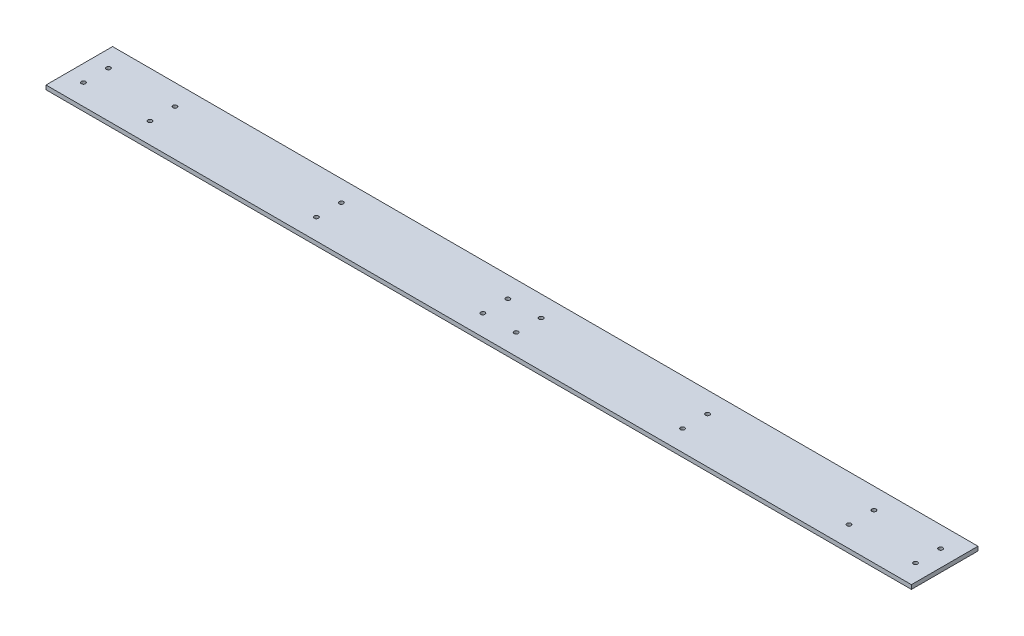
SolidWorks part; units mm, degrees
ref_plane "Front Plane" through (0, 0, 0) normal (0, 0, 1) x (1, 0, 0)
ref_plane "Top Plane" through (0, 0, 0) normal (0, 1, 0) x (1, 0, 0)
ref_plane "Right Plane" through (0, 0, 0) normal (1, 0, 0) x (0, 0, -1)
sketch "Sketch1" plane through (0, 0, 0) normal (0, 1, 0) x (1, 0, 0)
  line L0 (-200, 15) -> (-200, -15) construction
  line L1 (-500, 40) -> (540, 40)
  line L2 (-500, 40) -> (-500, -40)
  line L3 (-500, -40) -> (540, -40)
  line L4 (540, 40) -> (540, -40)
  line L5 (-200, 0) -> (0, 0) construction
  line L6 (0, 15) -> (0, -15) construction
  line L7 (240, 15) -> (240, -15) construction
  line L8 (0, 15) -> (40, 15) construction
  line L9 (40, 15) -> (40, -15) construction
  line L10 (40, -15) -> (0, -15) construction
  line L11 (0, 15) -> (-200, 15) construction
  line L12 (40, -15) -> (240, -15) construction
  line L13 (0, 0) -> (40, 0) construction
  line L14 (40, 0) -> (240, 0) construction
  line L15 (240, 0) -> (540, 0) construction
  line L16 (-200, 0) -> (-500, 0) construction
  line L17 (-400, 15) -> (-480, 15) construction
  line L18 (-480, 15) -> (-480, -15) construction
  line L19 (440, 15) -> (520, 15) construction
  line L20 (520, 15) -> (520, -15) construction
  circle A0 centre (0, 15) radius 2.5
  circle A1 centre (0, -15) radius 2.5
  circle A2 centre (40, 15) radius 2.5
  circle A3 centre (40, -15) radius 2.5
  circle A4 centre (-200, 15) radius 2.5
  circle A5 centre (-200, -15) radius 2.5
  circle A6 centre (240, -15) radius 2.5
  circle A7 centre (240, 15) radius 2.5
  circle A8 centre (-400, 15) radius 2.5
  circle A9 centre (-400, -15) radius 2.5
  circle A10 centre (440, -15) radius 2.5
  circle A11 centre (440, 15) radius 2.5
  circle A12 centre (520, 15) radius 2.5
  circle A13 centre (520, -15) radius 2.5
  circle A14 centre (-480, 15) radius 2.5
  circle A15 centre (-480, -15) radius 2.5
  dimension "D1" = 5
  dimension "D4" = 40
  dimension "D11" = 20
  dimension "D2" = 30
  dimension "D3" = 80
  dimension "D6" = 200
  dimension "D8" = 200
  dimension "D9" = 80
  dimension "D10" = 80
  dimension "D12" = 20
  dimension "D5" = 3
  dimension "D7" = 3
extrude "Boss-Extrude2" add sketch "Sketch1" along normal blind 5
equation "\"skin_sheetmetal_thickness\"= 0.80"
equation "\"base_width_skin_spacer\" = 50"
equation "\"base_width_skin_inner\" = \"base_width_skin_spacer\" + 2 * \"skin_sheetmetal_thickness\""
equation "\"base_width_skin_outer\" = \"base_width_skin_inner\" + 2 * \"skin_sheetmetal_thickness\""
equation "\"bend_cut_width\"= 3"
equation "\"bend_cut_length\"= 3"
equation "\"bend_offset_inner\"= 12.5"
equation "\"bend_offset_outer\" = \"bend_offset_inner\" + \"skin_sheetmetal_thickness\""
equation "\"border_offset_ends\"= 20"
equation "\"border_offset_sides\"= 10"
equation "\"border_offset_flange_horiz\"= 10"
equation "\"rivet_size\"= 4.3"
equation "\"rivet_offset_ends\"= 80"
equation "\"rivet_spacing_horiz\"= 200"
equation "\"rivet_spacing_vert\"= 30"
equation "\"rivet_spacing_offset_right\"= 40"
equation "\"base_length\"= 200"
